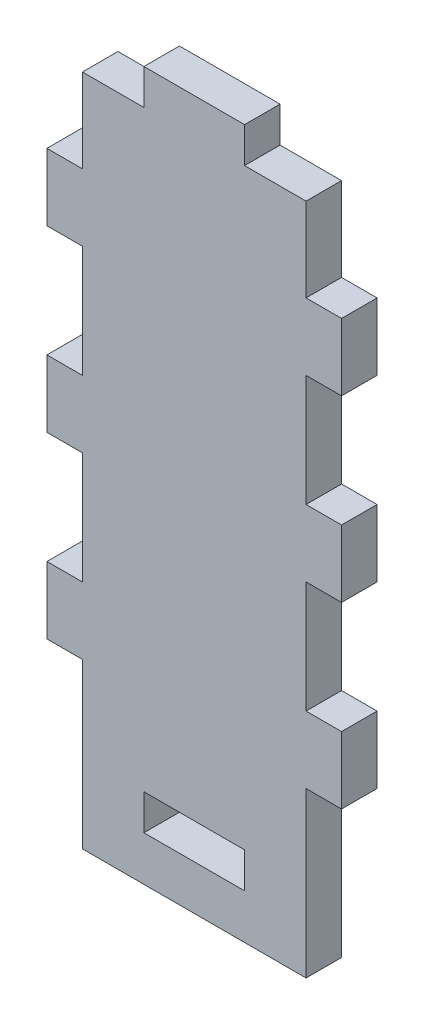
SolidWorks part; units mm, degrees
ref_plane "Front Plane" through (0, 0, 0) normal (0, 0, 1) x (1, 0, 0)
ref_plane "Top Plane" through (0, 0, 0) normal (0, 1, 0) x (1, 0, 0)
ref_plane "Right Plane" through (0, 0, 0) normal (1, 0, 0) x (0, 0, -1)
sketch "Sketch1" plane through (0, 0, 0) normal (0, 0, 1) x (1, 0, 0)
  line L0 (-5.5, 7.175) -> (0, 7.175) construction
  line L1 (0, 14.675) -> (3.175, 14.675)
  line L2 (3.175, 14.675) -> (3.175, 20.675)
  line L3 (3.175, 20.675) -> (0, 20.675)
  line L4 (0, 20.675) -> (0, 30.675)
  line L5 (0, 30.675) -> (3.175, 30.675)
  line L6 (3.175, 30.675) -> (3.175, 36.675)
  line L7 (3.175, 36.675) -> (0, 36.675)
  line L8 (0, 36.675) -> (0, 46.675)
  line L9 (0, 46.675) -> (3.175, 46.675)
  line L10 (3.175, 46.675) -> (3.175, 52.675)
  line L11 (3.175, 52.675) -> (0, 52.675)
  line L12 (0, 52.675) -> (0, 60.175)
  line L13 (0, 60.175) -> (-5.5, 60.175)
  line L14 (-5.5, 60.175) -> (-5.5, 63.35)
  line L15 (-5.5, 63.35) -> (-14.5, 63.35)
  line L16 (-14.5, 63.35) -> (-14.5, 60.175)
  line L17 (-14.5, 60.175) -> (-20, 60.175)
  line L18 (3.175, 30.0875) -> (-38.4558, 30.0875) construction
  line L19 (-10, 61.175) -> (-10, 29) construction
  line L20 (-20, 52.675) -> (-20, 60.175)
  line L21 (-23.175, 52.675) -> (-20, 52.675)
  line L22 (-23.175, 46.675) -> (-23.175, 52.675)
  line L23 (-20, 46.675) -> (-23.175, 46.675)
  line L24 (-20, 36.675) -> (-20, 46.675)
  line L25 (-23.175, 36.675) -> (-20, 36.675)
  line L26 (-23.175, 30.675) -> (-23.175, 36.675)
  line L27 (-20, 30.675) -> (-23.175, 30.675)
  line L28 (-20, 20.675) -> (-20, 30.675)
  line L29 (-23.175, 20.675) -> (-20, 20.675)
  line L30 (-23.175, 14.675) -> (-23.175, 20.675)
  line L31 (-20, 14.675) -> (-23.175, 14.675)
  line L32 (-14.5, 7.175) -> (-20, 7.175) construction
  line L33 (-20, 0) -> (0, 0)
  line L34 (-10, 0) -> (-10, 4)
  line L35 (-5.5, 4) -> (-5.5, 7.175)
  line L36 (-5.5, 7.175) -> (-14.5, 7.175)
  line L37 (-5.5, 4) -> (-14.5, 4)
  line L38 (-14.5, 4) -> (-14.5, 7.175)
  line L39 (-20, 7.175) -> (-20, 14.675)
  line L40 (-20, 7.175) -> (-20, 0)
  line L41 (0, 7.175) -> (0, 14.675)
  line L42 (0, 7.175) -> (0, 0)
  point P44 (-10, 7.175)
  dimension "D1" = 4
  dimension "D2" = 3.175
  dimension "D3" = 6
  dimension "D4" = 10
  dimension "D5" = 9
  dimension "D6" = 3.175
  dimension "D7" = 20
  dimension "D8" = 3.175
  dimension "D9" = 9
  dimension "D10" = 53
extrude "Boss-Extrude2" add sketch "Sketch1" along normal mid plane 3.175 contours L36 L35 L37 L33 L1 L2 L3 L4 L5 L6 L7 L8 L9 L10 L11 L12 L13 L14 L15 L16 L17 L20 L21 L22 L23 L24 L25 L26 L27 L28 L29 L30 L31 L38 region at (-10, 31.6168, 0)
